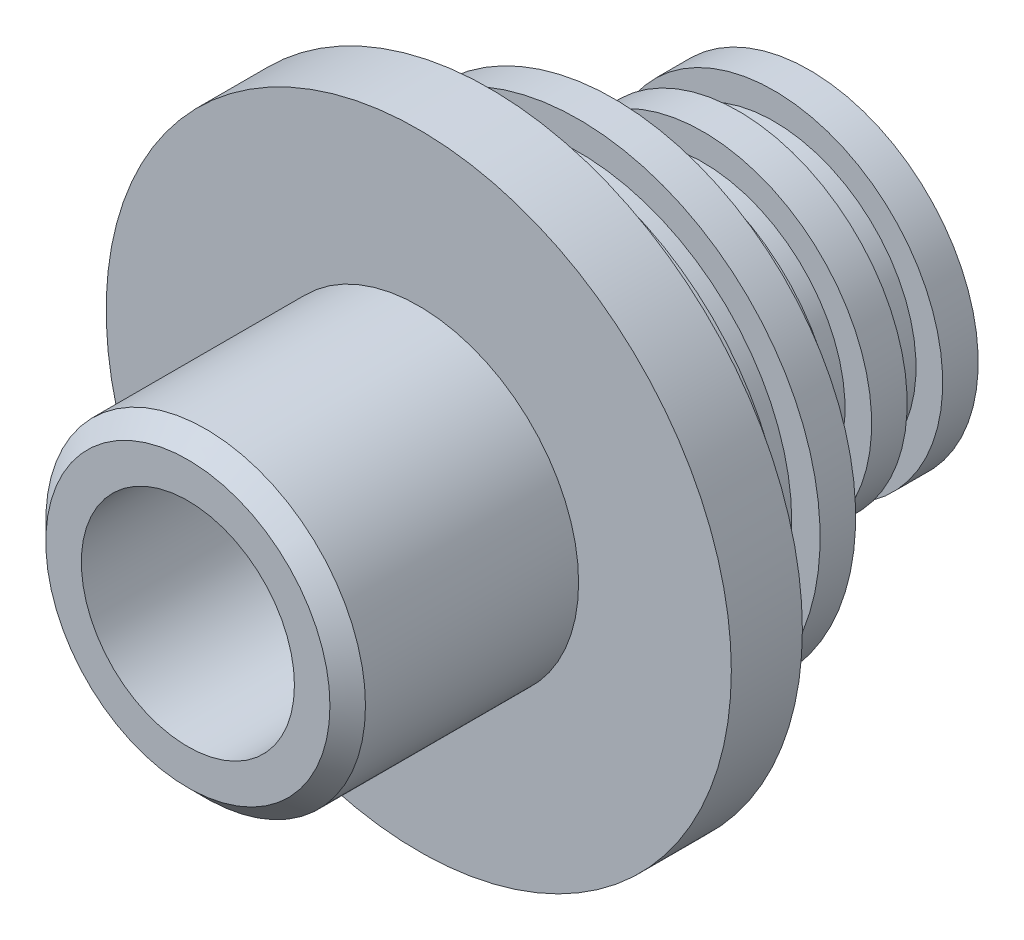
SolidWorks part; units mm, degrees
ref_plane "Front Plane" through (0, 0, 0) normal (0, 0, 1) x (1, 0, 0)
ref_plane "Top Plane" through (0, 0, 0) normal (0, 1, 0) x (1, 0, 0)
ref_plane "Right Plane" through (0, 0, 0) normal (1, 0, 0) x (0, 0, -1)
sketch "Sketch1" plane through (0, 0, 0) normal (0, 0, 1) x (1, 0, 0)
  circle A0 centre (0, 0) radius 8.8
  circle A1 centre (0, 0) radius 3
extrude "Boss-Extrude1" add sketch "Sketch1" along normal blind 17.5
sketch "Sketch2" plane through (0, 0, 17.5) normal (0, 0, 1) x (1, 0, 0)
  circle A0 centre (0, 0) radius 4.5
extrude "Cut-Extrude1" cut sketch "Sketch2" against normal blind 6.5 flip side to cut
sketch "Sketch3" plane through (0, 0, 0) normal (0, 0, -1) x (-1, 0, 0)
  circle A0 centre (0, 0) radius 6.8
extrude "Cut-Extrude2" cut sketch "Sketch3" against normal offset from surface (9 mm away) 2 flip side to cut up to face at (4.5, 0, 11)
sketch "Sketch5" plane through (0, 0, 0) normal (0, 0, -1) x (-1, 0, 0)
  circle A0 centre (0, 0) radius 4.75
extrude "Cut-Extrude3" cut sketch "Sketch5" against normal blind 5.5 flip side to cut
sketch "Sketch4" plane through (0, 0, 5.5) normal (0, 0, -1) x (-1, 0, 0)
  circle A1 centre (0, 0) radius 6
extrude "Cut-Extrude4" cut sketch "Sketch4" against normal blind 1 from offset 1 flip side to cut offset against normal yes
sketch "Sketch6" plane through (0, 0, 0) normal (0, 0, -1) x (-1, 0, 0)
  circle A0 centre (0, 0) radius 4
extrude "Cut-Extrude5" cut sketch "Sketch6" against normal blind 1 from offset 1 flip side to cut offset against normal yes
extrude "Cut-Extrude6" cut sketch "Sketch6<2>" against normal blind 1 from offset 3 flip side to cut offset against normal yes
sketch "Sketch6<2>" plane through (0, 0, 0) normal (0, 0, -1) x (-1, 0, 0) same geometry as "Sketch6"
chamfer "Chamfer1" distance 0.5 angle 45 1 edges at (4.5, 0, 17.5)
